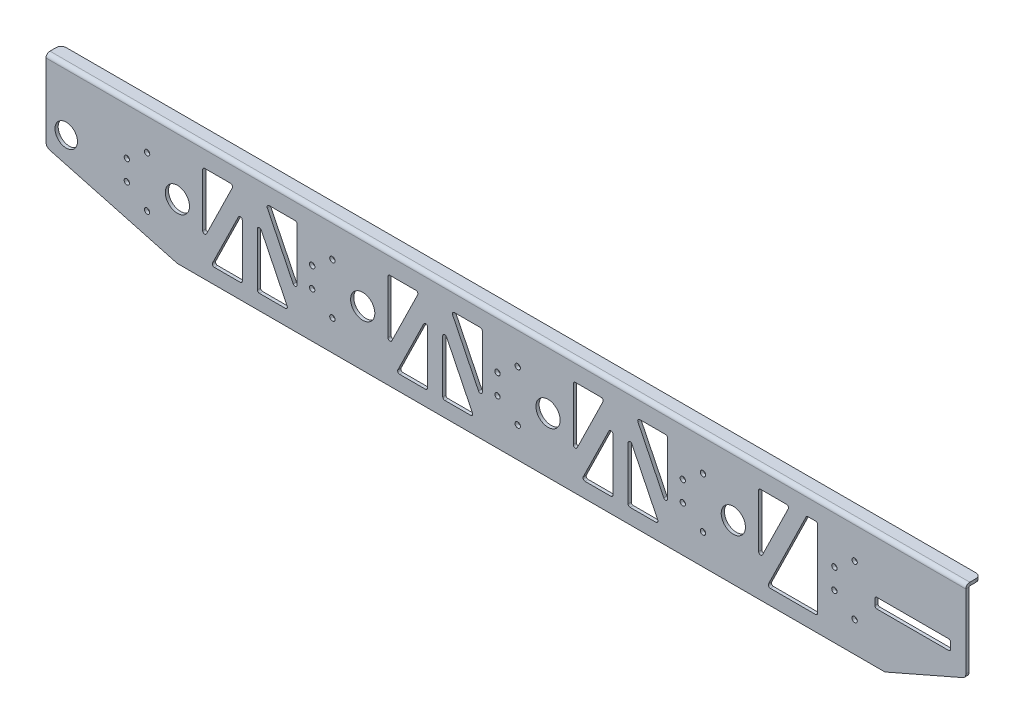
SolidWorks part; units mm, degrees
note: The reader was unsure of these and kept them because the rebuilt part matched: flange length of "Edge-Flange1".
material "5052-H32"
ref_plane "Front Plane" through (0, 0, 0) normal (0, 0, 1) x (1, 0, 0)
ref_plane "Top Plane" through (0, 0, 0) normal (0, 1, 0) x (1, 0, 0)
ref_plane "Right Plane" through (0, 0, 0) normal (1, 0, 0) x (0, 0, -1)
sketch "Sketch1" plane through (0, 0, 0) normal (0, 0, 1) x (1, 0, 0)
  line L0 (-30, 25) -> (100, 25) construction
  line L5 (-30, 25) -> (-30, -25) construction
  line L6 (70.7107, -70.7107) -> (0, 0) construction
  line L7 (-50, 10) -> (120, 10) construction
  line L8 (-50, 10) -> (-50, -10) construction
  line L9 (-50, -10) -> (120, -10) construction
  line L10 (120, 10) -> (120, -10) construction
  line L11 (0, 0) -> (100, 0) construction
  line L12 (254.044, -70.7107) -> (183.3333, 0) construction
  line L13 (123.3333, -20) -> (143.3333, -20) construction
  line L14 (123.3333, -20) -> (123.3333, 20) construction
  line L15 (123.3333, 20) -> (143.3333, 20) construction
  line L16 (143.3333, -20) -> (143.3333, 20) construction
  line L17 (437.3773, -70.7107) -> (366.6667, 0) construction
  line L18 (620.7107, -70.7107) -> (550, 0) construction
  line L20 (690, 5.01) -> (765, 5.01)
  line L21 (690, 5.01) -> (690, -5.01)
  line L22 (690, -5.01) -> (765, -5.01)
  line L23 (0, 0) -> (80.7856, -58.938) construction
  line L24 (-28.8068, 0) -> (750, 0) construction
  line L25 (-130, 60) -> (780, 60)
  line L27 (0, -55) -> (700, -55)
  line L28 (780, -20) -> (700, -55)
  line L29 (0, -55) -> (-130, -20)
  line L31 (-130, -20) -> (-130, 60)
  line L32 (780, 60) -> (780, -20)
  line L33 (765, 5.01) -> (765, -5.01)
  line L34 (-60, 40) -> (0, 0) construction
  circle A0 centre (0, 0) radius 11.9875
  circle A1 centre (-30, 25) radius 2.5 construction
  circle A3 centre (-30, -25) radius 2.5 construction
  circle A5 centre (-50, 10) radius 2.5 construction
  circle A6 centre (-50, -10) radius 2.5 construction
  circle A9 centre (100, 0) radius 40 construction
  arc A10 (100, 0) -> (70.7107, -70.7107) centre (0, 0) cw construction
  circle A11 centre (70.7107, -70.7107) radius 40 construction
  circle A12 centre (183.3333, 0) radius 11.9875
  circle A13 centre (153.3333, 25) radius 2.5 construction
  circle A14 centre (133.3333, 10) radius 2.5 construction
  circle A15 centre (133.3333, -10) radius 2.5 construction
  circle A16 centre (153.3333, -25) radius 2.5 construction
  circle A17 centre (366.6667, 0) radius 11.9875
  circle A18 centre (336.6667, 25) radius 2.5 construction
  circle A19 centre (316.6667, 10) radius 2.5 construction
  circle A20 centre (316.6667, -10) radius 2.5 construction
  circle A21 centre (336.6667, -25) radius 2.5 construction
  circle A22 centre (550, 0) radius 11.9875
  circle A23 centre (520, 25) radius 2.5 construction
  circle A24 centre (500, 10) radius 2.5 construction
  circle A25 centre (500, -10) radius 2.5 construction
  circle A26 centre (520, -25) radius 2.5 construction
  circle A27 centre (0, 0) radius 17.5 construction
  circle A28 centre (254.044, -70.7107) radius 40 construction
  circle A29 centre (437.3773, -70.7107) radius 40 construction
  circle A30 centre (620.7107, -70.7107) radius 40 construction
  circle A31 centre (-60, 40) radius 11 construction
  circle A34 centre (750, 0) radius 40 construction
  circle A35 centre (670, 25) radius 2.5 construction
  circle A36 centre (650, 10) radius 2.5 construction
  circle A37 centre (650, -10) radius 2.5 construction
  circle A38 centre (670, -25) radius 2.5 construction
  circle A42 centre (-110, 0) radius 11.1125
  circle A43 centre (-110, 0) radius 40 construction
  point P12 (133.3333, 20)
  point P20 (-50, 0)
  point P28 (-30, 0)
  point P66 (123.3333, 0)
  point P96 (690, 0)
  dimension "D1" = 23.975
  dimension "D6" = 50
  dimension "D7" = 5
  dimension "D2" = 170
  dimension "D9" = 4
  dimension "D11" = 80
  dimension "D12" = 100
  dimension "D17" = 550
  dimension "D20" = 35
  dimension "D5" = 22
  dimension "D26" = 20
  dimension "D34" = 150
  dimension "D15" = 20
  dimension "D21" = 110
  dimension "D22" = 22.225
  dimension "D23" = 75
  dimension "D3" = 20
  dimension "D4" = 130
  dimension "D8" = 30
  dimension "D10" = 20
  dimension "D13" = 45
  dimension "D14" = 60
  dimension "D16" = 60.7107
  dimension "D18" = 40
  dimension "D19" = 20
  dimension "D24" = 40
  dimension "D25" = 8.887
  dimension "D27" = 200
  dimension "D28" = 60
  dimension "D29" = 30
  dimension "D30" = 50
  dimension "D31" = 30
  dimension "D32" = 70
  dimension "D33" = 2
  dimension "D35" = 10.02
base flange "Base-Flange1" sketch "Sketch1" thickness 3.175 reverse thickness direction no parameters "D1"=0.7366
edge flange "Edge-Flange1" sketch "Sketch6" flange angle 90 flange length 15 flange position material inside bend radius 0.7366 thickness 3.175 parameters "D6"=10
sketch "Sketch6" plane through (0, 60, -3.175) normal (0, 1, 0) x (1, 0, 0)
  line L2 (-130, 0) -> (-130, 11.825)
  line L3 (-130, 11.825) -> (780, 11.825)
  line L4 (780, 11.825) -> (780, 0)
  line L7 (780, 0) -> (-130, 0) construction
  line L8 (780, 0) -> (-130, 0)
bend "EdgeBend1" bend radius 0.7366 bend angle 90 parameters "D5"=1
hole_wizard "M5 Clearance Hole1" positions "3DSketch1" profile "Sketch7" hole size "M5" standard "ANSI Metric" end condition up to next
sketch3d "3DSketch1"
  point P0 (-50, 10, 0)
  point P2 (-50, -10, 0)
  point P4 (-30, -25, 0)
  point P6 (-30, 25, 0)
  point P17 (133.3333, 10, 0)
  point P19 (133.3333, -10, 0)
  point P21 (153.3333, -25, 0)
  point P23 (153.3333, 25, 0)
  point P25 (316.6667, 10, 0)
  point P27 (316.6667, -10, 0)
  point P29 (336.6667, -25, 0)
  point P31 (336.6667, 25, 0)
  point P33 (500, 10, 0)
  point P35 (500, -10, 0)
  point P37 (520, -25, 0)
  point P39 (520, 25, 0)
  point P66 (650, 10, 0)
  point P68 (650, -10, 0)
  point P71 (670, 25, 0)
  point P73 (670, -25, 0)
sketch "Sketch7" plane through (-50, 10, 0) normal (1, 0, 0) x (0, -1, 0)
  line L0 (0, 0) -> (0, 3.175)
  line L1 (0, 3.175) -> (2.65, 3.175)
  line L2 (2.65, 3.175) -> (2.65, 0)
  line L5 (2.65, 0) -> (0, 0)
  line L11 (0, -6.35) -> (0, 107.95) construction
  dimension "Thru Hole Dia." = 5.3
  dimension "Thru Hole Depth" = 3.175
sketch "Sketch8" plane through (0, 0, 0) normal (0, 0, 1) x (1, 0, 0)
  line L0 (0, 0) -> (183.3333, 0) construction
  line L1 (183.3333, 0) -> (366.6667, 0) construction
  line L2 (366.6667, 0) -> (550, 0) construction
  line L3 (550, 0) -> (780, 0) construction
  line L4 (64.1667, 22.9434) -> (33.3506, -40)
  line L5 (25, 40) -> (118.3333, 40) construction
  line L6 (25, 40) -> (25, -40) construction
  line L7 (25, -40) -> (118.3333, -40) construction
  line L8 (118.3333, 40) -> (118.3333, -40) construction
  line L9 (64.1667, 40) -> (79.1667, 40) construction
  line L10 (64.1667, 40) -> (64.1667, -40) construction
  line L11 (64.1667, -40) -> (79.1667, -40) construction
  line L12 (79.1667, 40) -> (79.1667, -40) construction
  line L13 (55.8161, 40) -> (25, -22.9434)
  line L14 (71.6667, 40) -> (71.6667, -40)
  line L15 (25, -40) -> (64.1667, 40)
  line L16 (79.1667, 22.9434) -> (109.9827, -40)
  line L17 (87.5173, 40) -> (118.3333, -22.9434)
  line L18 (87.5173, 40) -> (118.3333, 40)
  line L19 (118.3333, 40) -> (118.3333, -22.9434)
  line L20 (55.8161, 40) -> (25, 40)
  line L21 (25, 40) -> (25, -22.9434)
  line L22 (64.1667, 22.9434) -> (64.1667, -40)
  line L23 (64.1667, -40) -> (33.3506, -40)
  line L24 (109.9827, -40) -> (79.1667, -40)
  line L25 (79.1667, -40) -> (79.1667, 22.9434)
  line L26 (301.6667, 40) -> (301.6667, -22.9434)
  line L27 (270.8506, 40) -> (301.6667, -22.9434)
  line L28 (270.8506, 40) -> (301.6667, 40)
  line L29 (262.5, -40) -> (262.5, 22.9434)
  line L30 (262.5, 22.9434) -> (293.3161, -40)
  line L31 (293.3161, -40) -> (262.5, -40)
  line L32 (247.5, -40) -> (216.6839, -40)
  line L33 (247.5, 22.9434) -> (216.6839, -40)
  line L34 (247.5, 22.9434) -> (247.5, -40)
  line L35 (208.3333, 40) -> (208.3333, -22.9434)
  line L36 (239.1494, 40) -> (208.3333, -22.9434)
  line L37 (239.1494, 40) -> (208.3333, 40)
  line L38 (485, 40) -> (485, -22.9434)
  line L39 (454.1839, 40) -> (485, -22.9434)
  line L40 (454.1839, 40) -> (485, 40)
  line L41 (445.8333, -40) -> (445.8333, 22.9434)
  line L42 (445.8333, 22.9434) -> (476.6494, -40)
  line L43 (476.6494, -40) -> (445.8333, -40)
  line L44 (430.8333, -40) -> (400.0173, -40)
  line L45 (430.8333, 22.9434) -> (400.0173, -40)
  line L46 (430.8333, 22.9434) -> (430.8333, -40)
  line L47 (391.6667, 40) -> (391.6667, -22.9434)
  line L48 (422.4827, 40) -> (391.6667, -22.9434)
  line L49 (422.4827, 40) -> (391.6667, 40)
  line L56 (614.1667, -40) -> (583.3506, -40)
  line L57 (614.1667, 22.9434) -> (583.3506, -40)
  line L58 (614.1667, 22.9434) -> (614.1667, -40)
  line L59 (575, 40) -> (575, -22.9434)
  line L60 (605.8161, 40) -> (575, -22.9434)
  line L61 (605.8161, 40) -> (575, 40)
  line L62 (629.1667, -40) -> (629.1667, 22.9434) [skipped]
  line L63 (629.1667, 22.9434) -> (659.9827, -40) [skipped]
  line L64 (659.9827, -40) -> (629.1667, -40) [skipped]
  line L65 (668.3333, 40) -> (668.3333, -22.9434) [skipped]
  line L66 (637.5173, 40) -> (668.3333, -22.9434) [skipped]
  line L67 (637.5173, 40) -> (668.3333, 40) [skipped]
  line L68 (780, -20) -> (780, 56.0884) construction
  line L69 (614.1667, -40) -> (633.3506, -40)
  line L70 (633.3506, -40) -> (633.3506, 40)
  line L71 (633.3506, 40) -> (622.5173, 40)
  line L72 (622.5173, 40) -> (614.1667, 22.9434)
  circle A0 centre (133.3333, 10) radius 2.65 construction
  point P16 (25, 0)
  point P23 (71.6667, 40)
  point P24 (71.6667, 40)
  dimension "D1" = 25
  dimension "D2" = 15
  dimension "D3" = 80
  dimension "D4" = 15
  dimension "D5" = 15
  dimension "D7" = 550
  dimension "D8" = 50
  dimension "D6" = 4
extrude "Cut-Extrude2" cut sketch "Sketch8" against normal up to next contours L20 L21 L13 | L23 L22 L4 | L25 L24 L16 | L19 L18 L17 | L36 L37 L35 | L34 L33 L32 | L31 L30 L29 | L28 L27 L26 | L48 L49 L47 | L46 L45 L44 | L43 L42 L41 | L40 L39 L38 | L60 L61 L59 | L58 L57 L56 | L71 L72 L58 L69 L70
sketch "Sketch9" plane through (0, 0, 0) normal (0, 0, 1) x (1, 0, 0)
  line L0 (0, 0) -> (-75.5656, 65.4969)
  line L3 (-99.7462, -7.1196) -> (-175.3118, 58.3773)
  line L4 (0, 0) -> (75.5656, -65.4969)
  line L5 (-99.7462, -7.1196) -> (0, 0)
  line L12 (-243.7195, -106.9181) -> (-183.7195, -106.9181)
  line L13 (-183.7195, -106.9181) -> (-234.6002, -20.83)
  line L14 (-234.6002, -20.83) -> (-294.6002, -20.83)
  line L15 (-294.6002, -20.83) -> (-243.7195, -106.9181)
  line L16 (-183.7195, -106.9181) -> (-183.7195, -43.7869) construction
  line L17 (-243.7195, -106.9181) -> (-243.7195, -170.0493) construction
  line L18 (-294.6002, -20.83) -> (-354.6002, -20.83)
  dimension "D1" = 100
  dimension "D2" = 100
  dimension "D3" = 100
  dimension "D4" = 60
  dimension "D5" = 135
  dimension "D8" = 100
  dimension "D10" = 60
  dimension "D11" = 100
  dimension "D14" = 60
fillet "Fillet1" radius 2 47 edges at (118.3333, -22.9434, -1.5875) (109.9827, -40, -1.5875) (79.1667, -40, -1.5875) (79.1667, 22.9434, -1.5875) (87.5173, 40, -1.5875) (118.3333, 40, -1.5875) (64.1667, 22.9434, -1.5875) (64.1667, -40, -1.5875) (33.3506, -40, -1.5875) (25, -22.9434, -1.5875) (55.8161, 40, -1.5875) (25, 40, -1.5875) (765, -5.01, -1.5875) (765, 5.01, -1.5875) (690, -5.01, -1.5875) (690, 5.01, -1.5875) (633.3506, -40, -1.5875) (583.3506, -40, -1.5875) (575, -22.9434, -1.5875) (605.8161, 40, -1.5875) (575, 40, -1.5875) (622.5173, 40, -1.5875) (633.3506, 40, -1.5875) (422.4827, 40, -1.5875) (430.8333, 22.9434, -1.5875) (445.8333, 22.9434, -1.5875) (400.0173, -40, -1.5875) (476.6494, -40, -1.5875) (445.8333, -40, -1.5875) (391.6667, -22.9434, -1.5875) (391.6667, 40, -1.5875) (454.1839, 40, -1.5875) (485, 40, -1.5875) (485, -22.9434, -1.5875) (430.8333, -40, -1.5875) (247.5, -40, -1.5875) (262.5, -40, -1.5875) (293.3161, -40, -1.5875) (216.6839, -40, -1.5875) (247.5, 22.9434, -1.5875) (262.5, 22.9434, -1.5875) (301.6667, -22.9434, -1.5875) (270.8506, 40, -1.5875) (301.6667, 40, -1.5875) (239.1494, 40, -1.5875) (208.3333, 40, -1.5875) (208.3333, -22.9434, -1.5875)
fillet "Fillet2" radius 5 6 edges at (700, -55, -1.5875) (780, -20, -1.5875) (780, 58.4125, -15) (-130, 58.4125, -15) (0, -55, -1.5875) (-130, -20, -1.5875)
sketch "Bend-Lines1" [suppressed] plane through (0, 0, 0) normal (0, 1, 0) x (1, 0, 0)
sketch "Bounding-Box1" [suppressed] plane through (0, 0, 0) normal (0, 1, 0) x (1, 0, 0)
sheet metal parameters "Sheet-Metal8" thickness 3.175 parameters "D1"=0.7366
flat pattern "Flat-Pattern8" [suppressed]
sketch "Bend-Lines2" plane through (0, 0, 0) normal (0, 1, 0) x (1, 0, 0)
sketch3d "Bounding-Box2" [suppressed]
  line L0 (-120, -55, 0) -> (870, -55, 0) construction
  line L1 (-120, 50, 0) -> (870, 50, 0) construction
  line L2 (-120, -55, 0) -> (-120, 50, 0) construction
  line L3 (870, -55, 0) -> (870, 50, 0) construction
sheet metal parameters "Sheet-Metal9" thickness 3.175 parameters "D1"=0.7366
flat pattern "Flat-Pattern8"
sketch "Bend-Lines2" plane through (0, 0, 0) normal (0, 0, 1) x (1, 0, 0)
  line L0 (870, 47.9137) -> (-120, 47.9137) construction
  line L1 (870, 47.9137) -> (-120, 47.9137) construction
sketch3d "Bounding-Box2" [suppressed]
  line L0 (-120, -55, 0) -> (870, -55, 0) construction
  line L1 (-120, 60.8275, 0) -> (870, 60.8275, 0) construction
  line L2 (-120, -55, 0) -> (-120, 60.8275, 0) construction
  line L3 (870, -55, 0) -> (870, 60.8275, 0) construction
bend of the flat pattern "Flatten-<EdgeBend1>1"
sheet metal parameters "Sheet-Metal10" thickness 3.175 parameters "D1"=0.7366
flat pattern "Flat-Pattern8"
sketch "Bend-Lines2" plane through (0, 0, 0) normal (0, 0, 1) x (1, 0, 0)
  line L0 (780, 57.9137) -> (-130, 57.9137) construction
  line L1 (780, 57.9137) -> (-130, 57.9137) construction
sketch3d "Bounding-Box2" [suppressed]
  line L0 (-130, -55, 0) -> (780, -55, 0) construction
  line L1 (-130, 70.8275, 0) -> (780, 70.8275, 0) construction
  line L2 (-130, -55, 0) -> (-130, 70.8275, 0) construction
  line L3 (780, -55, 0) -> (780, 70.8275, 0) construction
bend of the flat pattern "Flatten-<EdgeBend1>1"
sheet metal parameters "Sheet-Metal11" thickness 3.175 parameters "D1"=0.7366
flat pattern "Flat-Pattern8"
sketch "Bend-Lines2" plane through (0, 0, 0) normal (0, 0, 1) x (1, 0, 0)
  line L0 (780, 57.9137) -> (-130, 57.9137) construction
  line L1 (780, 57.9137) -> (-130, 57.9137) construction
sketch3d "Bounding-Box2" [suppressed]
  line L0 (-130, -55, 0) -> (780, -55, 0) construction
  line L1 (-130, 70.8275, 0) -> (780, 70.8275, 0) construction
  line L2 (-130, -55, 0) -> (-130, 70.8275, 0) construction
  line L3 (780, -55, 0) -> (780, 70.8275, 0) construction
bend of the flat pattern "Flatten-<EdgeBend1>1"
